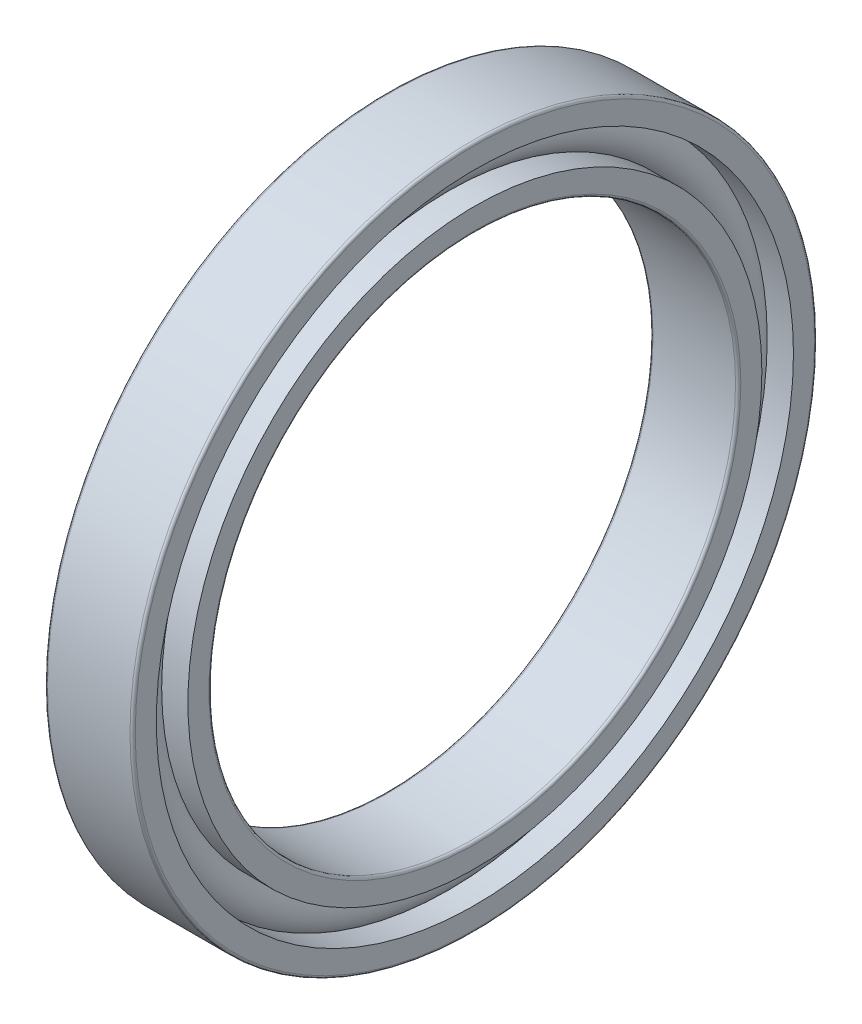
SolidWorks part; units mm, degrees
ref_plane "Plane1" through (0, 0, 0) normal (0, 0, 1) x (1, 0, 0)
ref_plane "Plane2" through (0, 0, 0) normal (0, 1, 0) x (1, 0, 0)
ref_plane "Plane3" through (0, 0, 0) normal (1, 0, 0) x (0, 0, -1)
sketch "Clipboard" plane through (0, 0, 0) normal (0, 0, 1) x (1, 0, 0)
  line L0 (-10, 0) -> (10, 0) construction
  line L1 (0, 0) -> (22.3471, -0.7804)
  line L2 (0, 0) -> (34.479, 1.204)
  line L3 (0, 0) -> (22.3471, -0.7804)
  line L4 (0, 0) -> (-22.3573, -0.3902)
  dimension "BallCLRad" = 34.5
sketch "CagSpiSke" plane through (0, 0, 0) normal (0, 0, 1) x (1, 0, 0)
  line L0 (0.27, 34.05) -> (0.27, 34.95)
  line L1 (0.27, 34.95) -> (-0.27, 34.95)
  line L2 (-0.27, 34.95) -> (-0.27, 34.05)
  line L3 (-0.27, 34.05) -> (0.27, 34.05)
  line L4 (-20.6375, 0) -> (20.6375, 0) construction
  line L5 (0, 0) -> (0, 23.7692) construction
  dimension "OD" = 69.9
  dimension "ID" = 68.1
revolve "CageSpine" add sketch "CagSpiSke" angle 0.001 about L4 reverse direction yes
ref_axis "Axis1" through (-50, 0, 0) along (1, 0, 0)
sketch "CagBalSke" plane through (0, 0, 0) normal (0, 0, 1) x (1, 0, 0)
  line L0 (-2.97, 34.5) -> (2.97, 34.5)
  line L1 (-1.905, 34.5) -> (1.905, 34.5) construction
  line L2 (-10, 0) -> (10, 0) construction
  line L3 (0, 0) -> (0, 24) construction
  arc A0 (2.97, 34.5) -> (-2.97, 34.5) centre (0, 34.5) cw
  dimension "BallCLRad" = 34.5
revolve "CageBall" [suppressed] add sketch "CagBalSke" angle 360 about L1 reverse direction yes
pattern_circular "CageBalls" [suppressed] count 2 every 180 about axis through (-50, 0, 0) along (1, 0, 0)
sketch "CagTrmODSke" plane through (0, 0, 0) normal (0, 0, 1) x (1, 0, 0)
  line L0 (2.971, 34.95) -> (2.971, 37.471)
  line L1 (2.971, 37.471) -> (-2.971, 37.471)
  line L2 (-2.971, 37.471) -> (-2.971, 34.95)
  line L3 (-2.971, 34.95) -> (2.971, 34.95)
  line L4 (-20.6375, 0) -> (20.6375, 0) construction
  line L5 (0, 0) -> (0, 25) construction
  dimension "Width" = 5.942
  dimension "ID" = 69.9
  dimension "OD" = 74.942
revolve "CageTrimOD" [suppressed] cut sketch "CagTrmODSke" angle 360 about L4 reverse direction yes
sketch "CagTrmIDSke" plane through (0, 0, 0) normal (0, 0, 1) x (1, 0, 0)
  line L0 (2.971, 31.531) -> (2.971, 34.05)
  line L1 (2.971, 34.05) -> (-2.971, 34.05)
  line L2 (-2.971, 34.05) -> (-2.971, 31.531)
  line L3 (-2.971, 31.531) -> (2.971, 31.531)
  line L4 (-20.6375, 0) -> (20.6375, 0) construction
  line L5 (0, 0) -> (0, 25) construction
  dimension "Width" = 5.942
  dimension "ID" = 63.062
  dimension "OD" = 68.1
revolve "CageTrimID" [suppressed] cut sketch "CagTrmIDSke" angle 360 about L4 reverse direction yes
sketch "BalSimSke" plane through (0, 0, 0) normal (0, 0, 1) x (1, 0, 0)
  line L0 (-10, 0) -> (10, 0) construction
  line L1 (-10, 34.5) -> (10, 34.5) construction
  line L2 (0, 0) -> (0, 23) construction
  circle A0 centre (0, 34.5) radius 2.7
  dimension "BallCLRad" = 34.5
  dimension "Ball_diameter" = 5.4
revolve "BallsSimplified" add sketch "BalSimSke" angle 360 about L0
sketch "BalDetSke" plane through (0, 0, 0) normal (0, 0, 1) x (1, 0, 0)
  line L0 (-2.7, 34.5) -> (2.7, 34.5)
  line L1 (-1.905, 34.5) -> (1.905, 34.5) construction
  line L2 (0, 0) -> (0, 25) construction
  arc A0 (2.7, 34.5) -> (-2.7, 34.5) centre (0, 34.5) cw
  dimension "BallCLRad" = 34.5
  dimension "Ball_diameter" = 5.4
revolve "BallDetailed" [suppressed] add sketch "BalDetSke" angle 360 about L1 reverse direction yes
sketch "InnRacSke" plane through (0, 0, 0) normal (0, 0, 1) x (1, 0, 0)
  line L0 (-1.9788, 32.7) -> (-5, 32.7)
  line L1 (-5, 32.7) -> (-5, 30.3)
  line L2 (-4.7, 30) -> (4.7, 30)
  line L3 (5, 30.3) -> (5, 32.7)
  line L4 (5, 32.7) -> (1.9788, 32.7)
  line L5 (-20.6375, 0) -> (20.6375, 0) construction
  line L6 (0, 0) -> (0, 30) construction
  arc A0 (-5, 30.3) -> (-4.7, 30) centre (-4.7, 30.3) ccw
  arc A1 (4.7, 30) -> (5, 30.3) centre (4.7, 30.3) ccw
  arc A2 (1.9788, 32.7) -> (-1.9788, 32.7) centre (0, 34.5) cw
  dimension "BallCLRad" = 34.5
  dimension "Fillet_radius" = 0.3
  dimension "Ball_diameter" = 5.35
  dimension "ID" = 60
  dimension "OD" = 65.4
  dimension "Width" = 10
revolve "InnerRace" add sketch "InnRacSke" angle 360 about L5 reverse direction yes
sketch "OutRacSke" plane through (0, 0, 0) normal (0, 0, 1) x (1, 0, 0)
  line L0 (-1.9788, 36.3) -> (-5, 36.3)
  line L1 (-5, 36.3) -> (-5, 38.7)
  line L2 (-4.7, 39) -> (4.7, 39)
  line L3 (5, 38.7) -> (5, 36.3)
  line L4 (5, 36.3) -> (1.9788, 36.3)
  line L5 (-20.6375, 0) -> (20.6375, 0) construction
  line L6 (0, 0) -> (0, 30) construction
  arc A0 (-5, 38.7) -> (-4.7, 39) centre (-4.7, 38.7) cw
  arc A1 (4.7, 39) -> (5, 38.7) centre (4.7, 38.7) cw
  arc A2 (1.9788, 36.3) -> (-1.9788, 36.3) centre (0, 34.5) ccw
  dimension "BallCLRad" = 34.5
  dimension "Fillet_radius" = 0.3
  dimension "Ball_diameter" = 5.35
  dimension "Width" = 10
revolve "OuterRace" add sketch "OutRacSke" angle 360 about L5 reverse direction yes
pattern_circular "BallsDetailed" [suppressed] count 2 every 180 about axis through (-50, 0, 0) along (1, 0, 0)
equation "\"BallCLRad@Clipboard\" = ( \"OD@OutRacSke\" + \"ID@InnRacSke\" ) / 4"
equation "\"BallCLRad@BalSimSke\" = \"BallCLRad@Clipboard\""
equation "\"BallCLRad@BalDetSke\" = \"BallCLRad@Clipboard\""
equation "\"BallCLRad@InnRacSke\" = \"BallCLRad@Clipboard\""
equation "\"BallCLRad@OutRacSke\" = \"BallCLRad@Clipboard\""
equation "\"Ball_diameter@InnRacSke\" = \"Ball_diameter@BalDetSke\" - 0.05"
equation "\"Ball_diameter@OutRacSke\" = \"Ball_diameter@BalDetSke\" - 0.05"
equation "\"Ball_diameter@BalSimSke\" = \"Ball_diameter@BalDetSke\""
equation "\"Width@OutRacSke\" = \"Width@InnRacSke\""
equation "\"Fillet_radius@OutRacSke\" = \"Fillet_radius@InnRacSke\""
equation "\"Max_count@Clipboard\" = int( 3.14159265 / atn(( \"Ball_diameter@BalDetSke\" / 2) / sqr( \"BallCLRad@Clipboard\"  *  \"BallCLRad@Clipboard\" - ( \"Ball_diameter@BalDetSke\" / 2) *  ( \"Ball_diameter@BalDetSke\" / 2))))"
equation "\"Max_count@Clipboard\" = ((sgn( \"Max_count@Clipboard\" - \"Count@Clipboard\" )-1)*( \"Max_count@Clipboard\" - \"Count@Clipboard\" ))/-2+ \"Count@Clipboard\""
equation "\"Count@BallsDetailed\" = int( \"Show_count@Clipboard\" ) "
equation "\"Count@BallsDetailed\" = ((sgn( \"Count@BallsDetailed\" - \"Max_count@Clipboard\" )-1)*( \"Count@BallsDetailed\" - \"Max_count@Clipboard\" ))/-2+ \"Max_count@Clipboard\""
equation "\"Count@BallsDetailed\" = ((sgn( \"Count@BallsDetailed\" - \"Min_count@Clipboard\" )+1)*( \"Count@BallsDetailed\" - \"Min_count@Clipboard\"))/2 +\"Min_count@Clipboard\""
equation "\"Angle@BallsDetailed\" = 360.0 / \"Max_count@Clipboard\""
equation "\"BallCLRad@CagBalSke\" = \"BallCLRad@Clipboard\""
equation "\"Count@CageBalls\" = \"Count@BallsDetailed\""
equation "\"Angle@CageBalls\" = \"Angle@BallsDetailed\""
equation "\"Angle@CageSpine\" =  \"Angle@CageBalls\" * ( \"Count@CageBalls\" -1 + int( \"Count@CageBalls\" / \"Max_count@Clipboard\" ) )  + 0.001 -  int( \"Count@CageBalls\" / \"Max_count@Clipboard\" ) * 0.001"
equation "\"Angle@CageSpine\" =  \"Angle@CageSpine\" * int( \"Min_count@Clipboard\" / 2) + int(1 / \"Min_count@Clipboard\")  * 0.001"
equation "\"CageWallOD@CagBalSke\" =  \"Ball_diameter@BalDetSke\" * 1.1"
equation "\"Thickness@CagSpiSke\" =  \"Ball_diameter@BalDetSke\" * 0.1"
equation "\"OD@CagTrmODSke\" = \"BallCLRad@Clipboard\" * 2 + \"CageWallOD@CagBalSke\" + 0.002"
equation "\"ID@CagTrmODSke\" = \"BallCLRad@Clipboard\" * 2 + \"Ball_diameter@BalDetSke\" / 6"
equation "\"OD@CagTrmIDSke\" = \"BallCLRad@Clipboard\" * 2 - \"Ball_diameter@BalDetSke\" / 6"
equation "\"ID@CagTrmIDSke\" = \"BallCLRad@Clipboard\" * 2 - \"CageWallOD@CagBalSke\" + 0.002"
equation "\"OD@CagSpiSke\" = \"ID@CagTrmODSke\""
equation "\"ID@CagSpiSke\" = \"OD@CagTrmIDSke\""
equation "\"Width@CagTrmODSke\" = \"CageWallOD@CagBalSke\" + 0.002"
equation "\"Width@CagTrmIDSke\" = \"CageWallOD@CagBalSke\" + 0.002"
